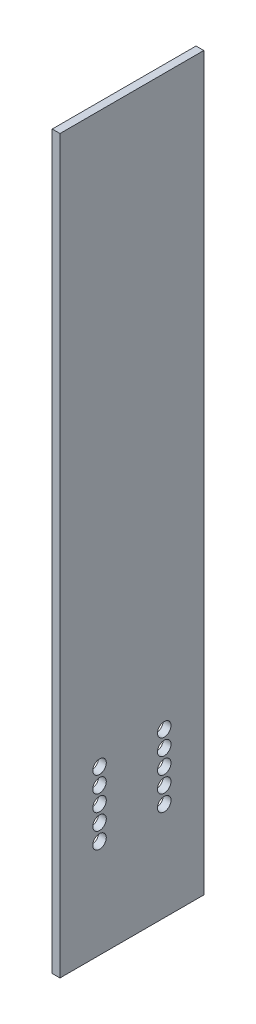
SolidWorks part; units mm, degrees
ref_plane "Front Plane" through (0, 0, 0) normal (0, 0, 1) x (1, 0, 0)
ref_plane "Top Plane" through (0, 0, 0) normal (0, 1, 0) x (1, 0, 0)
ref_plane "Right Plane" through (0, 0, 0) normal (1, 0, 0) x (0, 0, -1)
sketch "Sketch1" plane through (0, 0, 0) normal (1, 0, 0) x (0, 0, -1)
  line L1 (-28.2194, 143.51) -> (28.2194, 143.51)
  line L2 (-28.2194, 143.51) -> (-28.2194, -143.51)
  line L3 (-28.2194, -143.51) -> (28.2194, -143.51)
  line L4 (28.2194, 143.51) -> (28.2194, -143.51)
  line L5 (-28.2194, 143.51) -> (28.2194, -143.51) construction
  line L6 (-28.2194, -143.51) -> (28.2194, 143.51) construction
  point P0 (0, 0)
  dimension "D1" = 56.4388
  dimension "D2" = 287.02
extrude "Boss-Extrude1" add sketch "Sketch1" along normal blind 3.048
sketch "Sketch2" plane through (3.048, 0, 0) normal (1, 0, 0) x (0, 0, -1)
  line L0 (0, 143.51) -> (0, -143.51) construction
  line L1 (28.2194, 143.51) -> (-28.2194, 143.51) construction
  line L2 (-28.2194, -143.51) -> (28.2194, -143.51) construction
  point P0 (-12.7, -98.5012)
  point P9 (12.7, -98.5012)
  dimension "D1" = 12.7
  dimension "D2" = 45.0088
hole_wizard "#4 (0.209) Diameter Hole1" positions "Sketch3" profile "Sketch4" hole size "#4" standard "ANSI Inch" end condition through all
sketch "Sketch3" plane through (3.048, 0, 0) normal (1, 0, 0) x (0, 0, -1)
  point P0 (-12.7, -98.5012)
  point P3 (12.7, -98.5012)
sketch "Sketch4" plane through (3.048, -98.5012, 12.7) normal (0, 1, 0) x (0, 0, -1)
  line L0 (0, 0) -> (0, 3.048)
  line L1 (0, 3.048) -> (2.6543, 3.048)
  line L2 (2.6543, 3.048) -> (2.6543, 0)
  line L5 (2.6543, 0) -> (0, 0)
  line L11 (0, -6.35) -> (0, 107.95) construction
  dimension "Thru Hole Dia." = 5.3086
  dimension "Thru Hole Depth" = 3.048
pattern_linear "LPattern1" count 4 spacing 6.35 along (0, 1, 0) count 2 spacing 6.35 along (0, -1, 0) of "#4 (0.209) Diameter Hole1" pattern seed only yes
equation "\"motor offset\"=6mm"
equation "\"thickness0.25\"=0.225in"
equation "\"thickness0.125\"=0.122in"
equation "\"thickness_acrylic0.1\"= 0.1in"
equation "\"D1@Sketch1\"=\"thickness_acrylic0.1\"+\"thickness0.125\"+2"
equation "\"D2@Sketch2\"=\"thickness0.125\" + 0.5 +1.15"
